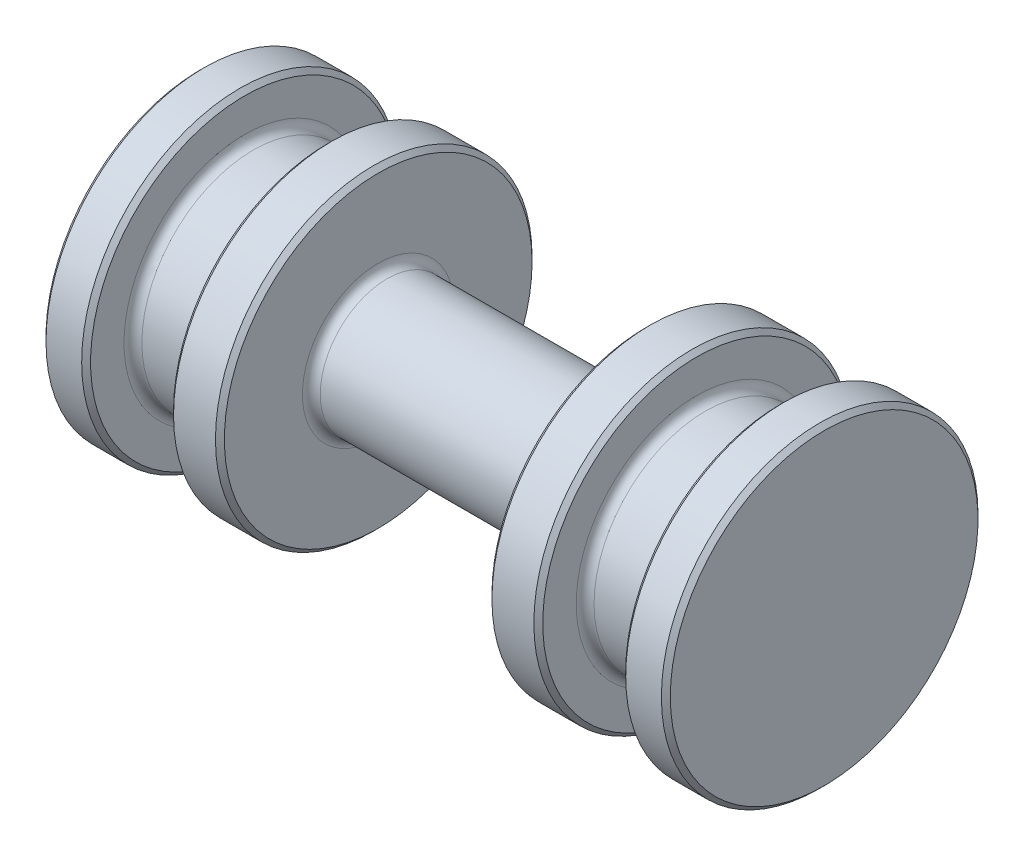
SolidWorks part; units mm, degrees
material "6063-T6"
ref_plane "Front Plane" through (0, 0, 0) normal (0, 0, 1) x (1, 0, 0)
ref_plane "Top Plane" through (0, 0, 0) normal (0, 1, 0) x (1, 0, 0)
ref_plane "Right Plane" through (0, 0, 0) normal (1, 0, 0) x (0, 0, -1)
sketch "Sketch1" plane through (0, 0, 0) normal (1, 0, 0) x (0, 0, -1)
  circle A0 centre (0, 0) radius 4.5085
  dimension "D1" = 9.017
extrude "Boss-Extrude1" add sketch "Sketch1" along normal blind 22.86
sketch "Sketch2" plane through (0, 0, 0) normal (0, 0, 1) x (1, 0, 0)
  line L0 (-1.6174, 0) -> (23.3579, 0) construction
  line L1 (1.27, 4.5085) -> (3.6322, 4.5085)
  line L2 (3.6322, 4.5085) -> (3.6322, 3.175)
  line L3 (3.6322, 3.175) -> (1.27, 3.175)
  line L4 (1.27, 3.175) -> (1.27, 4.5085)
  line L5 (0, 4.5085) -> (0, -4.5085) construction
  line L6 (17.78, 5.6982) -> (17.78, -5.5364) construction
  line L7 (22.86, -4.5085) -> (22.86, 4.5085) construction
  line L8 (19.2278, 4.5085) -> (21.59, 4.5085)
  line L9 (21.59, 4.5085) -> (21.59, 3.175)
  line L10 (21.59, 3.175) -> (19.2278, 3.175)
  line L11 (19.2278, 3.175) -> (19.2278, 4.5085)
  line L12 (14.1478, 4.5085) -> (16.51, 4.5085)
  line L13 (16.51, 4.5085) -> (16.51, 3.175)
  line L14 (16.51, 3.175) -> (14.1478, 3.175)
  line L15 (14.1478, 3.175) -> (14.1478, 4.5085)
  line L17 (5.08, 4.5085) -> (12.7, 4.5085)
  line L18 (5.08, 4.5085) -> (5.08, 1.905)
  line L19 (5.08, 1.905) -> (12.7, 1.905)
  line L20 (12.7, 4.5085) -> (12.7, 1.905)
  dimension "D1" = 9.017
  dimension "D2" = 6.35
  dimension "D3" = 2.3622
  dimension "D4" = 1.27
  dimension "D5" = 5.08
  dimension "D6" = 1.27
  dimension "D7" = 6.35
  dimension "D8" = 5.08
  dimension "D9" = 10.16
  dimension "D10" = 3.81
revolve "Cut-Revolve1" cut sketch "Sketch2" angle 360 about L0
fillet "Fillet1" radius 0.254 8 edges at (21.59, 0, 3.175) (19.2278, 0, 3.175) (16.51, 0, 3.175) (14.1478, 0, 3.175) (12.7, 0, 1.905) (5.08, 0, 1.905) (3.6322, 0, 3.175) (1.27, 0, 3.175)
chamfer "Chamfer1" distance 0.127 angle 45 5 edges at (12.7, 0, 4.5085) (0, 0, -4.5085) (21.59, 0, 4.5085) (16.51, 0, 4.5085) (3.6322, 0, 4.5085)
chamfer "Chamfer2" distance 0.127 angle 45 5 edges at (22.86, 0, -4.5085) (19.2278, 0, 4.5085) (14.1478, 0, 4.5085) (5.08, 0, 4.5085) (1.27, 0, 4.5085)
sketch "Sketch3" plane through (22.86, 0, 0) normal (1, 0, 0) x (0, 0, -1)
  circle A0 centre (0, 0) radius 7.9117
extrude "reduce-vent" cut sketch "Sketch3" against normal offset from surface (5.08 mm away) 1.27 up to face at (16.51, 0, 4.3815)
chamfer "vent-edge-break" distance 0.127 angle 45 1 edges at (17.78, 0, 4.5085)
